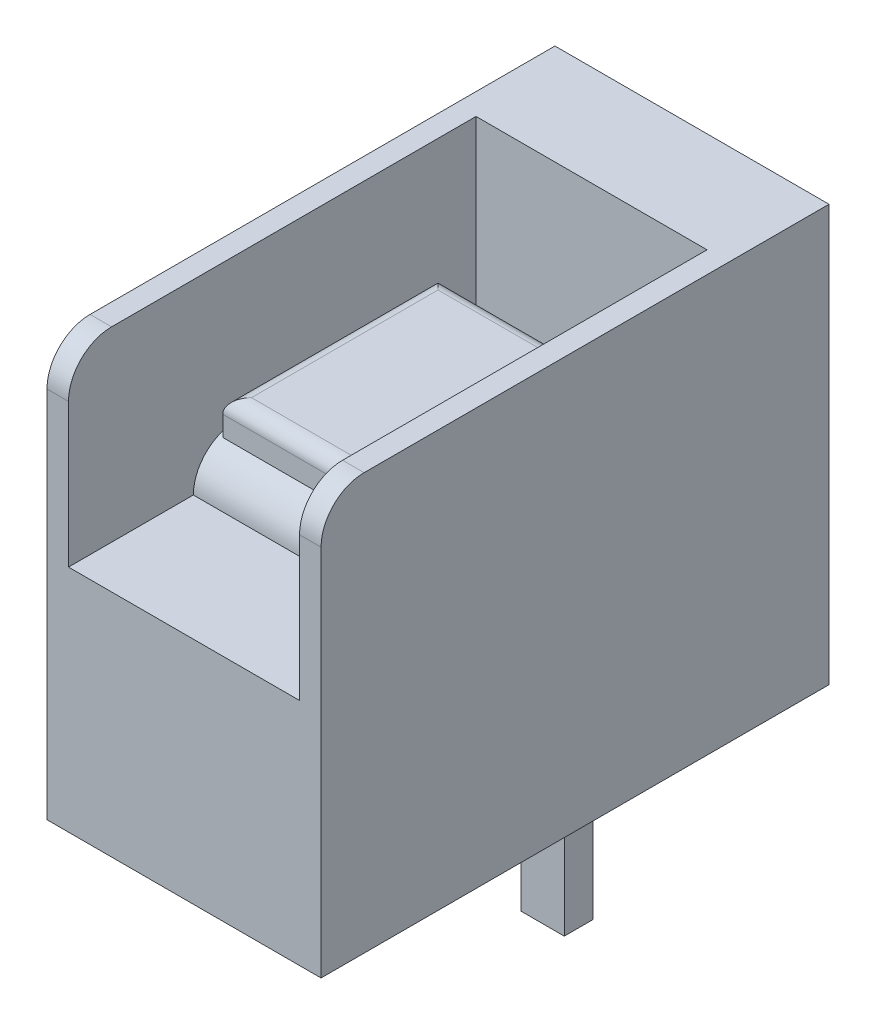
SolidWorks part; units mm, degrees
ref_plane "前视基准面" through (0, 0, 0) normal (0, 0, 1) x (1, 0, 0)
ref_plane "上视基准面" through (0, 0, 0) normal (0, 1, 0) x (1, 0, 0)
ref_plane "右视基准面" through (0, 0, 0) normal (1, 0, 0) x (0, 0, -1)
sketch "草图1" plane through (0, 0, 0) normal (0, 1, 0) x (1, 0, 0)
  line L0 (0, 14.1902) -> (0, -10.6155) construction
  line L1 (-22.4154, 0) -> (19.6333, 0) construction
  line L3 (-4.775, 8.85) -> (4.775, 8.85)
  line L4 (-4.775, 8.85) -> (-4.775, -8.85)
  line L5 (-4.775, -8.85) -> (4.775, -8.85)
  line L6 (4.775, 8.85) -> (4.775, -8.85)
  dimension "D1" = 9.55
  dimension "D2" = 17.7
extrude "拉伸1" add sketch "草图1" along normal blind 14.5
sketch "草图2" plane through (0, 14.5, 0) normal (0, 1, 0) x (-1, 0, 0)
  line L0 (-4.025, -5.35) -> (4.025, -5.35)
  line L1 (4.775, 8.85) -> (-4.775, 8.85) construction
  line L2 (-4.025, 8.85) -> (4.025, 8.85)
  line L3 (-4.025, 8.85) -> (-4.025, -5.35)
  line L4 (-4.775, -8.85) -> (4.775, -8.85) construction
  line L8 (4.025, 8.85) -> (4.025, -5.35)
  line L10 (4.775, -8.85) -> (4.775, 8.85) construction
  line L11 (-4.775, 8.85) -> (-4.775, -8.85) construction
  dimension "D1" = 0.75
  dimension "D2" = 0.75
  dimension "D3" = 3.5
extrude "切除-拉伸1" cut sketch "草图2" against normal blind 6.5
sketch "草图5" plane through (0, 0, -8.85) normal (0, 0, -1) x (-1, 0, 0)
  line L1 (-4.025, 13.3) -> (4.025, 13.3)
  line L2 (-4.025, 13.3) -> (-4.025, 0)
  line L3 (-4.025, 0) -> (4.025, 0)
  line L4 (4.025, 13.3) -> (4.025, 0)
  line L5 (4.025, 8) -> (4.025, 14.5) construction
  line L6 (-4.025, 8) -> (-4.025, 14.5) construction
  line L7 (-4.775, 0) -> (4.775, 0) construction
  line L8 (-4.775, 14.5) -> (4.775, 14.5) construction
  dimension "D1" = 1.2
extrude "切除-拉伸4" cut sketch "草图5" against normal blind 2.5
fillet "圆角1" radius 1.5 2 edges at (4.4, 14.5, 8.85) (-4.4, 14.5, 8.85)
sketch "草图8" plane through (0, 8, 0) normal (0, 1, 0) x (-1, 0, 0)
  line L0 (-4.025, 8.85) -> (-4.025, -5.35) construction
  line L1 (-4.025, -4.5) -> (4.025, -4.5)
  line L2 (-4.025, -4.5) -> (-4.025, 4.5)
  line L3 (-4.025, 4.5) -> (4.025, 4.5)
  line L4 (4.025, -4.5) -> (4.025, 4.5)
  line L5 (4.025, -5.35) -> (4.025, 7.35) construction
  line L6 (5.894, 0) -> (-6.1893, 0) construction
  dimension "D1" = 9
extrude "卡片" add sketch "草图8" along normal blind 1.5
fillet "圆角2" radius 1.5 2 edges at (0, 9.5, -4.5) (0, 9.5, 4.5)
sketch "草图10" plane through (0, 9.5, 0) normal (0, 1, 0) x (-1, 0, 0)
  line L1 (0, 8.0097) -> (0, -7.6912) construction
  line L2 (-3.75, 3.75) -> (3.75, 3.75)
  line L3 (-3.75, 3.75) -> (-3.75, -3.75)
  line L4 (-3.75, -3.75) -> (3.75, -3.75)
  line L6 (-6.3124, 0) -> (6.1893, 0) construction
  line L7 (3.75, 3.75) -> (3.75, -3.75)
  dimension "D1" = 7.5
  dimension "D2" = 7.5
extrude "拉伸4" add sketch "草图10" along normal blind 1.2
fillet "圆角4" radius 0.5 4 edges at (3.75, 10.7, 0) (-3.75, 10.7, 0) (0, 10.7, -3.75) (0, 10.7, 3.75)
sketch "草图11" plane through (0, 0, 0) normal (0, -1, 0) x (1, 0, 0)
  line L0 (0, 13.6785) -> (0, -13.919) construction
  line L2 (-0.75, -3.65) -> (0.75, -3.65)
  line L3 (-0.75, -3.65) -> (-0.75, -4.65)
  line L4 (-0.75, -4.65) -> (0.75, -4.65)
  line L5 (0.75, -3.65) -> (0.75, -4.65)
  line L6 (-4.025, -8.85) -> (-4.775, -8.85) construction
  dimension "D1" = 5.2
  dimension "D2" = 1.5
  dimension "D3" = 1
extrude "凸台-拉伸1" add sketch "草图11" along normal blind 7
